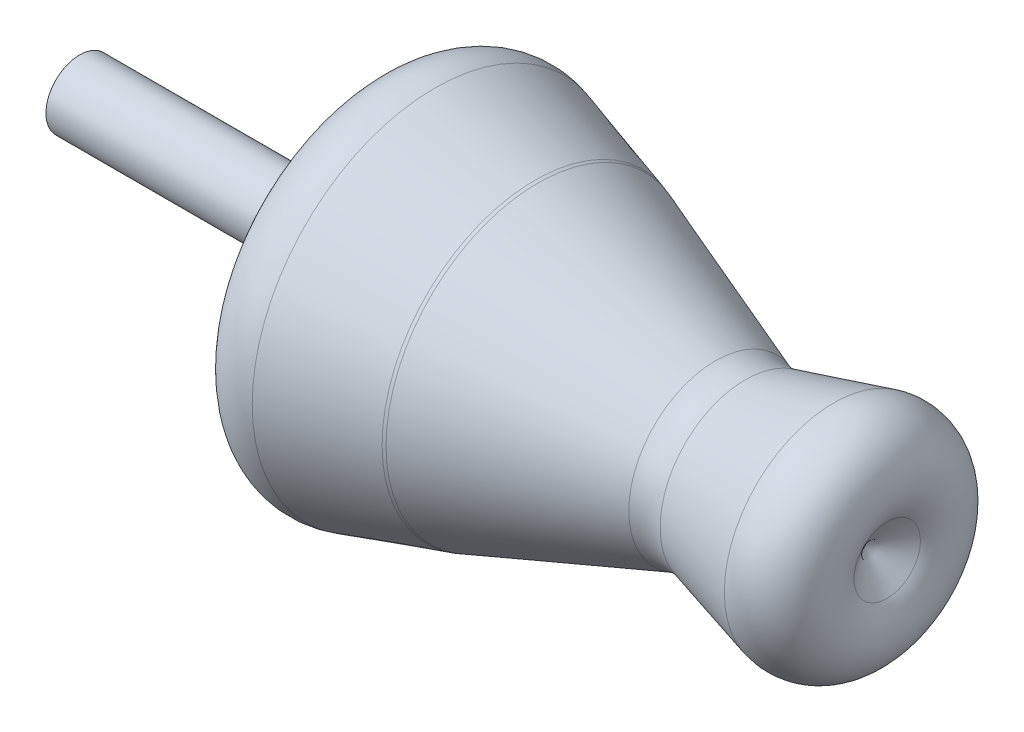
SolidWorks part; units mm, degrees
material "Szkło"
ref_plane "Płaszczyzna przednia" through (0, 0, 0) normal (0, 0, 1) x (1, 0, 0)
ref_plane "Płaszczyzna górna" through (0, 0, 0) normal (0, 1, 0) x (1, 0, 0)
ref_plane "Płaszczyzna prawa" through (0, 0, 0) normal (1, 0, 0) x (0, 0, -1)
sketch "Szkic1" plane through (0, 0, 0) normal (0, 0, 1) x (1, 0, 0)
  line L0 (-114.3098, 6.8087) -> (-60.0318, 6.8087)
  line L1 (-60.0318, 6.8087) -> (-52.9354, 39.9892)
  line L2 (-52.9354, 39.9892) -> (-22.0564, 30.7831)
  line L3 (-22.0564, 30.7831) -> (17.0697, 16.3985)
  line L4 (17.0697, 16.3985) -> (64.4431, 29.2487)
  line L5 (64.4431, 29.2487) -> (44.1128, 0)
  line L6 (44.1128, 0) -> (-114.3098, 0) construction
  line L7 (-114.3098, 6.8087) -> (-114.3098, 0)
  line L8 (-114.3098, 0) -> (44.1128, 0)
revolve "Obrót1" add sketch "Szkic1" angle 360 about L6
fillet "Zaokrąglenie1" radius 10 3 edges at (-22.0564, 0, -30.7831) (64.4431, 0, -29.2487) (17.0697, 0, -16.3985)
fillet "Zaokrąglenie3" radius 10 2 edges at (-52.9354, 0, -39.9892) (-60.0318, 0, -6.8087)
